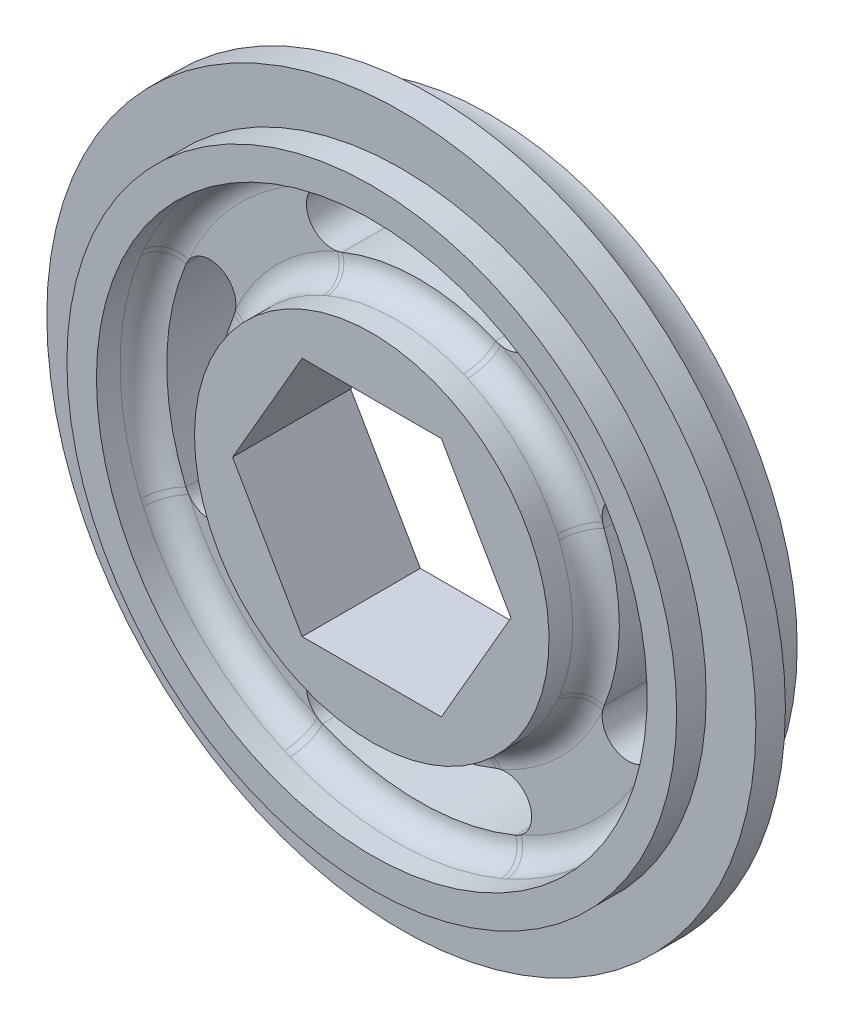
SolidWorks part; units mm, degrees
ref_plane "Front Plane" through (0, 0, 0) normal (0, 0, 1) x (1, 0, 0)
ref_plane "Top Plane" through (0, 0, 0) normal (0, 1, 0) x (1, 0, 0)
ref_plane "Right Plane" through (0, 0, 0) normal (1, 0, 0) x (0, 0, -1)
sketch "Sketch1" plane through (0, 0, 0) normal (0, 0, 1) x (1, 0, 0)
  line L1 (-7.479, 0) -> (-3.7395, -6.477)
  line L2 (-3.7395, -6.477) -> (3.7395, -6.477)
  line L3 (3.7395, -6.477) -> (7.479, 0)
  line L4 (7.479, 0) -> (3.7395, 6.477)
  line L5 (3.7395, 6.477) -> (-3.7395, 6.477)
  line L6 (-3.7395, 6.477) -> (-7.479, 0)
  circle A0 centre (0, 0) radius 6.477 construction
  circle A1 centre (0, 0) radius 19.05
  dimension "D1" = 38.1
  dimension "D2" = 12.954
extrude "Hex Axel Cutout & Outside Rim" add sketch "Sketch1" along normal blind 12.7
sketch "Sketch3" plane through (0, 0, 12.7) normal (0, 0, 1) x (1, 0, 0)
  circle A0 centre (0, 0) radius 16.383
  circle A1 centre (0, 0) radius 19.05
  dimension "D1" = 32.766
extrude "Pipe Step" cut sketch "Sketch3" against normal blind 1.5875
ref_plane "Mid Plane" through (0, 0, 6.35) normal (0, 0, 1) x (1, 0, 0)
mirror "Step Mirror" about plane through (0, 0, 6.35) normal (0, 0, 1) of "Pipe Step"
ref_axis "Center Axis" through (0, 0, 11.1125) along (0, 0, -1)
sketch "Sketch4" plane through (0, 0, 0) normal (1, 0, 0) x (0, 0, -1)
  line L0 (-1.5875, -19.05) -> (-1.5875, 19.05) construction
  line L1 (-1.5875, -19.05) -> (-1.5875, 19.05) construction
  line L2 (-11.1125, 19.05) -> (-11.1125, -19.05) construction
  line L3 (-11.1125, 19.05) -> (-11.1125, -19.05) construction
  line L4 (-1.5875, 19.05) -> (-11.1125, 19.05) construction
  line L5 (-3.175, 19.05) -> (-9.525, 19.05)
  line L6 (-3.175, 19.05) -> (-9.525, 19.05) construction
  line L7 (-6.35, 19.05) -> (-6.35, 16.51) construction
  arc A1 (-3.175, 19.05) -> (-9.525, 19.05) centre (-6.35, 19.7644) cw
  dimension "D1" = 6.35
  dimension "D2" = 2.54
revolve "Poly Cord Groove" cut sketch "Sketch4" angle 360 about axis through (0, 0, 11.1125) along (0, 0, -1)
sketch "Sketch5" plane through (0, 0, 0) normal (0, 0, -1) x (-1, 0, 0)
  circle A0 centre (0, 0) radius 9.525
  circle A1 centre (0, 0) radius 14.7955
  circle A2 centre (0, 0) radius 16.383 construction
  dimension "D1" = 1.5875
extrude "Spoke Step" cut sketch "Sketch5" against normal blind 2.54
mirror "Spoke Step Mirror" about plane through (0, 0, 6.35) normal (0, 0, 1) of "Spoke Step"
sketch "Sketch6" plane through (0, 0, 10.16) normal (0, 0, 1) x (1, 0, 0)
  line L0 (9.525, 0) -> (14.7955, 0) construction
  arc A0 (11.2346, -4.6535) -> (11.2346, 4.6535) centre (0, 0) ccw construction
  arc A1 (12.5253, -5.1881) -> (12.5253, 5.1881) centre (0, 0) ccw
  circle A2 centre (0, 0) radius 9.525 construction
  circle A3 centre (0, 0) radius 14.7955 construction
  arc A4 (9.9439, -4.1189) -> (9.9439, 4.1189) centre (0, 0) ccw
  arc A5 (9.9439, -4.1189) -> (12.5253, -5.1881) centre (11.2346, -4.6535) ccw
  arc A6 (12.5253, 5.1881) -> (9.9439, 4.1189) centre (11.2346, 4.6535) ccw
  arc A7 (-4.6535, -11.2346) -> (4.6535, -11.2346) centre (0, 0) ccw construction
  arc A8 (-5.1881, -12.5253) -> (5.1881, -12.5253) centre (0, 0) ccw
  arc A9 (-4.1189, -9.9439) -> (4.1189, -9.9439) centre (0, 0) ccw
  arc A10 (-4.1189, -9.9439) -> (-5.1881, -12.5253) centre (-4.6535, -11.2346) ccw
  arc A11 (5.1881, -12.5253) -> (4.1189, -9.9439) centre (4.6535, -11.2346) ccw
  arc A12 (-11.2346, 4.6535) -> (-11.2346, -4.6535) centre (0, 0) ccw construction
  arc A13 (-12.5253, 5.1881) -> (-12.5253, -5.1881) centre (0, 0) ccw
  arc A14 (-9.9439, 4.1189) -> (-9.9439, -4.1189) centre (0, 0) ccw
  arc A15 (-9.9439, 4.1189) -> (-12.5253, 5.1881) centre (-11.2346, 4.6535) ccw
  arc A16 (-12.5253, -5.1881) -> (-9.9439, -4.1189) centre (-11.2346, -4.6535) ccw
  arc A17 (4.6535, 11.2346) -> (-4.6535, 11.2346) centre (0, 0) ccw construction
  arc A18 (5.1881, 12.5253) -> (-5.1881, 12.5253) centre (0, 0) ccw
  arc A19 (4.1189, 9.9439) -> (-4.1189, 9.9439) centre (0, 0) ccw
  arc A20 (4.1189, 9.9439) -> (5.1881, 12.5253) centre (4.6535, 11.2346) ccw
  arc A21 (-5.1881, 12.5253) -> (-4.1189, 9.9439) centre (-4.6535, 11.2346) ccw
  point P9 (12.1602, 0)
  point P14 (12.1602, 0)
  point P20 (0, -12.1602)
  point P27 (-12.1602, 0)
  point P34 (0, 12.1602)
  point P39 (0, 0)
  dimension "D1" = 4
extrude "Slots" cut sketch "Sketch6" against normal through all
fillet "Fillet1" radius 1.27 4 edges at (-9.525, 0, 10.16) (-14.7955, 0, 10.16) (-9.525, 0, 2.54) (-14.7955, 0, 2.54)
sketch "Sketch7" plane through (0, 0, 6.35) normal (0, 0, 1) x (1, 0, 0)
  line L1 (23.9973, 33.2603) -> (-26.4119, 33.2603)
  line L2 (23.9973, 33.2603) -> (23.9973, -40.0267)
  line L3 (23.9973, -40.0267) -> (-26.4119, -40.0267)
  line L4 (-26.4119, 33.2603) -> (-26.4119, -40.0267)
extrude "MidCut" cut sketch "Sketch7" against normal through all
